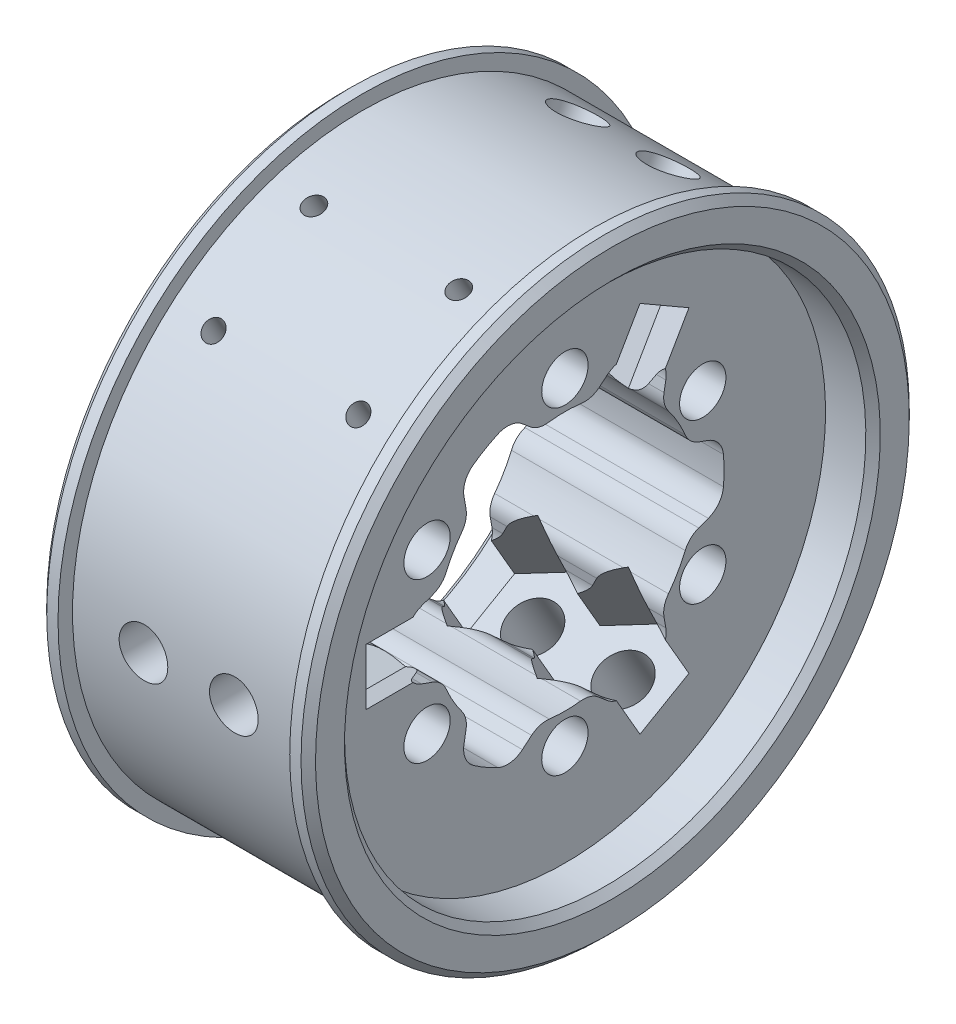
SolidWorks part; units mm, degrees
ref_plane "Front Plane" through (0, 0, 0) normal (0, 0, 1) x (1, 0, 0)
ref_plane "Top Plane" through (0, 0, 0) normal (0, 1, 0) x (1, 0, 0)
ref_plane "Right Plane" through (0, 0, 0) normal (1, 0, 0) x (0, 0, -1)
sketch "Sketch1" plane through (0, 0, 0) normal (0, 0, 1) x (1, 0, 0)
  line L0 (0, 0) -> (0, 31.75)
  line L1 (0, 31.75) -> (12.7, 31.75)
  line L2 (12.7, 31.75) -> (12.7, 33.3375)
  line L3 (12.7, 33.3375) -> (14.732, 33.3375)
  line L4 (14.732, 33.3375) -> (14.732, 0)
  line L5 (14.732, 0) -> (0, 0)
  dimension "D1" = 12.7
  dimension "D2" = 2.032
  dimension "D3" = 1.5875
  dimension "D4" = 31.75
revolve "Revolve1" add sketch "Sketch1" angle 360 about L5
sketch "Sketch2" plane through (14.732, 0, 0) normal (1, 0, 0) x (0, 0, -1)
  line L0 (14.6656, 4.0824) -> (15.7207, 3.6983)
  line L1 (14.6656, -4.0824) -> (15.7207, -3.6983)
  line L2 (0, 0) -> (25.6394, 0) construction
  line L3 (3.6486, -14.6171) -> (4.6575, -15.4637)
  line L4 (10.8682, -10.6596) -> (11.0632, -11.7654)
  line L5 (-10.8345, -10.4683) -> (-11.0632, -11.7654)
  line L6 (-3.6486, -14.6171) -> (-4.6575, -15.4637)
  line L7 (-14.4831, 4.1488) -> (-15.7207, 3.6983)
  line L8 (-14.4831, -4.1488) -> (-15.7207, -3.6983)
  line L9 (-3.7974, 14.7419) -> (-4.6575, 15.4637)
  line L10 (-10.8345, 10.4683) -> (-11.0632, 11.7654)
  line L11 (10.8682, 10.6596) -> (11.0632, 11.7654)
  line L12 (3.7974, 14.7419) -> (4.6575, 15.4637)
  circle A0 centre (0, 0) radius 17.4498 construction
  circle A1 centre (0, 17.4498) radius 2.54
  circle A2 centre (15.112, 8.7249) radius 2.54
  circle A3 centre (15.112, -8.7249) radius 2.54
  circle A4 centre (0, -17.4498) radius 2.54
  circle A5 centre (-15.112, -8.7249) radius 2.54
  circle A6 centre (-15.112, 8.7249) radius 2.54
  circle A7 centre (0, 0) radius 14.2875 construction
  arc A9 (17.3822, 1.5349) -> (17.3822, -1.5349) centre (0, 0) cw
  arc A11 (10.0204, -14.2859) -> (7.3618, -15.8209) centre (0, 0) cw
  arc A12 (-7.3618, -15.8209) -> (-10.0204, -14.2859) centre (0, 0) cw
  arc A13 (-17.3822, -1.5349) -> (-17.3822, 1.5349) centre (0, 0) cw
  arc A14 (-10.0204, 14.2859) -> (-7.3618, 15.8209) centre (0, 0) cw
  arc A15 (7.3618, 15.8209) -> (10.0204, 14.2859) centre (0, 0) cw
  arc A16 (11.3516, -8.6761) -> (13.1895, -5.4927) centre (0, 0) ccw
  arc A18 (-1.709, -14.0414) -> (1.709, -14.0414) centre (0, 0) ccw
  arc A19 (-13.0148, -5.5407) -> (-11.3057, -8.5008) centre (0, 0) ccw
  arc A20 (-11.3057, 8.5008) -> (-13.0148, 5.5407) centre (0, 0) ccw
  arc A21 (1.8379, 14.1688) -> (-1.8379, 14.1688) centre (0, 0) ccw
  arc A22 (13.1895, 5.4927) -> (11.3516, 8.6761) centre (0, 0) ccw
  arc A23 (13.1895, 5.4927) -> (14.6656, 4.0824) centre (15.5343, 6.4692) ccw
  arc A24 (11.3516, 8.6761) -> (10.8682, 10.6596) centre (13.3696, 10.2185) cw
  arc A25 (11.0632, 11.7654) -> (10.0204, 14.2859) centre (8.5618, 12.2065) ccw
  arc A26 (7.3618, 15.8209) -> (4.6575, 15.4637) centre (6.2902, 13.518) ccw
  arc A27 (3.7974, 14.7419) -> (1.8379, 14.1688) centre (2.1647, 16.6877) cw
  arc A28 (-1.8379, 14.1688) -> (-3.7974, 14.7419) centre (-2.1647, 16.6877) cw
  arc A29 (-4.6575, 15.4637) -> (-7.3618, 15.8209) centre (-6.2902, 13.518) ccw
  arc A30 (-10.0204, 14.2859) -> (-11.0632, 11.7654) centre (-8.5618, 12.2065) ccw
  arc A31 (-10.8345, 10.4683) -> (-11.3057, 8.5008) centre (-13.3359, 10.0272) cw
  arc A32 (-13.0148, 5.5407) -> (-14.4831, 4.1488) centre (-15.3518, 6.5356) cw
  arc A33 (-15.7207, 3.6983) -> (-17.3822, 1.5349) centre (-14.852, 1.3115) ccw
  arc A34 (-17.3822, -1.5349) -> (-15.7207, -3.6983) centre (-14.852, -1.3115) ccw
  arc A35 (-14.4831, -4.1488) -> (-13.0148, -5.5407) centre (-15.3518, -6.5356) cw
  arc A36 (-11.3057, -8.5008) -> (-10.8345, -10.4683) centre (-13.3359, -10.0272) cw
  arc A37 (-11.0632, -11.7654) -> (-10.0204, -14.2859) centre (-8.5618, -12.2065) ccw
  arc A38 (-7.3618, -15.8209) -> (-4.6575, -15.4637) centre (-6.2902, -13.518) ccw
  arc A39 (-3.6486, -14.6171) -> (-1.709, -14.0414) centre (-2.0159, -16.5628) cw
  arc A40 (1.709, -14.0414) -> (3.6486, -14.6171) centre (2.0159, -16.5628) cw
  arc A41 (4.6575, -15.4637) -> (7.3618, -15.8209) centre (6.2902, -13.518) ccw
  arc A42 (10.0204, -14.2859) -> (11.0632, -11.7654) centre (8.5618, -12.2065) ccw
  arc A43 (10.8682, -10.6596) -> (11.3516, -8.6761) centre (13.3696, -10.2185) cw
  arc A44 (13.1895, -5.4927) -> (14.6656, -4.0824) centre (15.5343, -6.4692) cw
  arc A45 (15.7207, -3.6983) -> (17.3822, -1.5349) centre (14.852, -1.3115) ccw
  arc A46 (17.3822, 1.5349) -> (15.7207, 3.6983) centre (14.852, 1.3115) ccw
  point P18 (0, 0)
  point P45 (0, 0)
  point P52 (13.5661, 4.4825)
  point P61 (2.9011, 13.9899)
  point P92 (13.5661, -4.4825)
  point P95 (17.1585, -3.175)
  point P98 (17.1585, 3.175)
  dimension "D1" = 34.8996
  dimension "D2" = 5.08
  dimension "D4" = 28.575
  dimension "D5" = 20
  dimension "D7" = 6.35
  dimension "D9" = 2.54
  dimension "D10" = 2.54
  dimension "D6" = 20
  dimension "D3" = 6
  dimension "D8" = 6
mirror "Mirror3" about plane through (0, 0, 0) normal (-1, 0, 0) of "Revolve1"
extrude "Cut-Extrude3" cut sketch "Sketch2" against normal through all
sketch "Sketch3" plane through (14.732, 0, 0) normal (1, 0, 0) x (0, 0, -1)
  circle A0 centre (0, 0) radius 28.575
  dimension "D1" = 57.15
extrude "Cut-Extrude4" cut sketch "Sketch3" against normal blind 5.207
sketch "Sketch4" plane through (-14.732, 0, 0) normal (-1, 0, 0) x (0, 0, 1)
  circle A0 centre (0, 0) radius 22.86
  dimension "D1" = 45.72
extrude "Cut-Extrude5" cut sketch "Sketch4" against normal blind 5.207 contours A0
chamfer "Chamfer1" distance 0.7937 angle 45 4 edges at (-14.732, -22.86, 0) (-14.732, 33.3375, 0) (14.732, 33.3375, 0) (14.732, 28.575, 0)
ref_plane "Plane2" through (0, 0, 17.3822) normal (0, 0, 1) x (1, 0, 0)
ref_plane "Plane3" through (0, -15.0534, 8.6911) normal (0, -0.866, 0.5) x (-1, 0, 0)
sketch "Sketch7" plane through (0, 0, 17.3822) normal (0, 0, 1) x (1, 0, 0)
  line L1 (-4.9213, 5.6826) -> (-9.8425, 2.8413)
  line L2 (-9.8425, 2.8413) -> (-9.8425, -2.8413)
  line L3 (-9.8425, -2.8413) -> (-4.9212, -5.6826)
  line L4 (-4.9212, -5.6826) -> (0, -2.8413)
  line L6 (0, 2.8413) -> (-4.9213, 5.6826)
  line L7 (4.9848, 5.7192) -> (0, 2.8413)
  line L9 (0, -2.8413) -> (4.9848, -5.7192)
  line L10 (4.9848, -5.7192) -> (9.9378, -2.8596)
  line L11 (9.9378, -2.8596) -> (9.9377, 2.8596)
  line L12 (9.9377, 2.8596) -> (4.9848, 5.7192)
  line L13 (-9.525, 1.5349) -> (-9.525, -1.5349) construction
  line L14 (9.525, -1.5349) -> (-9.525, -1.5349) construction
  line L15 (0, -2.9139) -> (0, 2.8053) [skipped]
  line L16 (0.0318, 2.8596) -> (0.0318, -2.8596) [skipped]
  circle A0 centre (-4.9213, 0) radius 4.9212 construction
  circle A1 centre (4.9848, 0) radius 4.953 construction
  point P12 (0, -1.5349)
  point P23 (-9.525, 0)
  dimension "D1" = 9.906
  dimension "D2" = 9.906
extrude "Cut-Extrude6" cut sketch "Sketch7" along normal blind 9.525 from offset 5.08 offset against normal yes
sketch "Sketch10" plane through (0, 0, 21.8272) normal (0, 0, -1) x (-1, 0, 0)
  line L0 (-4.9848, 5.7192) -> (-4.9848, -5.7192) construction
  line L1 (4.9213, 5.6826) -> (4.9212, -5.6826) construction
  circle A0 centre (-4.9848, 0) radius 2.667
  circle A1 centre (4.9213, 0) radius 2.667
  dimension "D1" = 5.334
extrude "Cut-Extrude9" cut sketch "Sketch10" against normal through all
ref_plane "Plane4" through (0, -7.0207, 12.1603) normal (0, -0.5, 0.866) x (1, 0, 0)
sketch "Sketch11" plane through (0, -21.2872, -2.1063) normal (0, 0.866, -0.5) x (1, 0, 0)
  line L0 (11.6525, -12.4677) -> (-11.6712, -12.4677) construction
  line L4 (-12.7, -44.2177) -> (-12.7, 19.2823) construction
  line L5 (12.7, 19.2823) -> (12.7, -44.2177) construction
  circle A0 centre (-7.9375, -6.1177) radius 1.0922
  circle A1 centre (-7.9375, -18.8177) radius 1.0922
  circle A2 centre (7.9375, -18.8177) radius 1.0922
  circle A3 centre (7.9375, -6.1177) radius 1.0922
  dimension "D1" = 2.1844
  dimension "D2" = 4.7625
  dimension "D3" = 4.7625
  dimension "D5" = 6.35
  dimension "D6" = 6.35
pattern_circular "CirPattern2" count 3 every 120 about axis through (12.7, 0, 0) along (1, 0, 0) of "Cut-Extrude9", "Cut-Extrude6"
extrude "Cut-Extrude10" cut sketch "Sketch11" against normal through all
ref_plane "Plane5" through (0, -1.5315, 0.8936) normal (0, -0.8637, 0.504) x (-1, 0, 0)
pattern_circular "CirPattern3" count 3 every 120 about axis through (-12.7, 0, 0) along (1, 0, 0) of "Cut-Extrude10"
